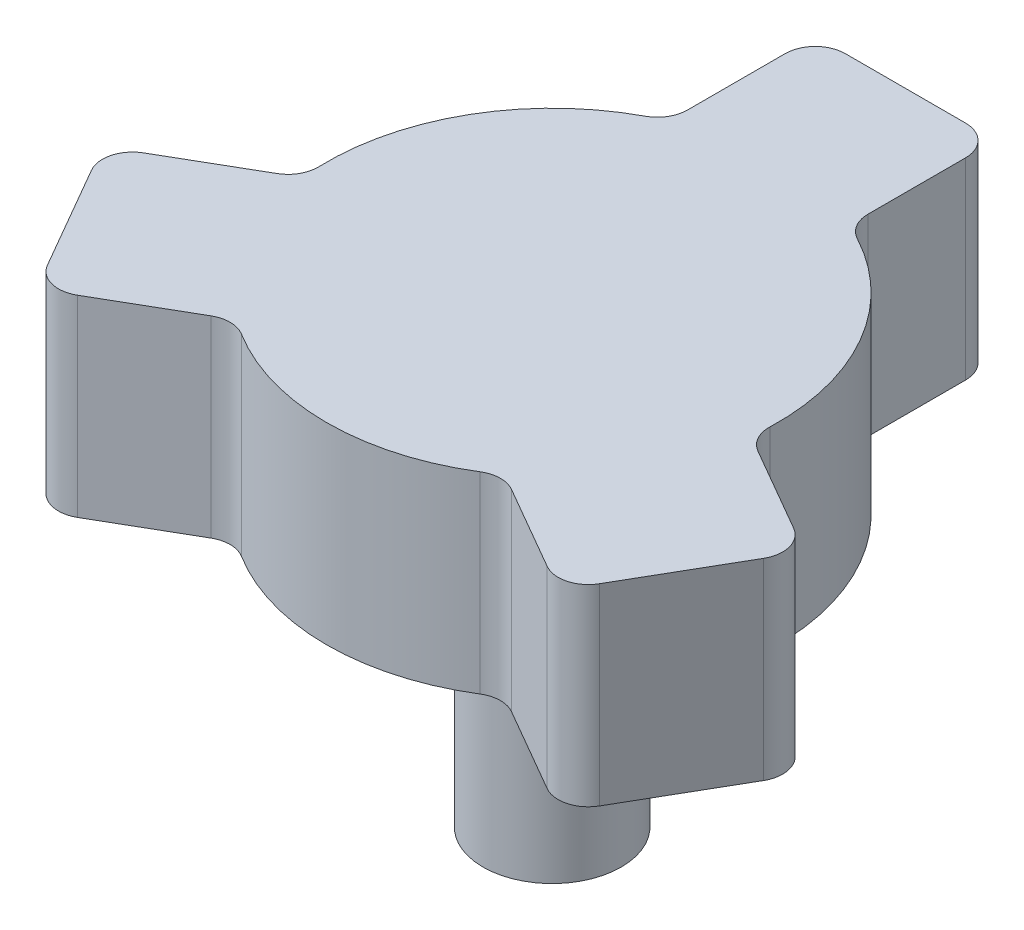
SolidWorks part; units mm, degrees
ref_plane "Front Plane" through (0, 0, 0) normal (0, 0, 1) x (1, 0, 0)
ref_plane "Top Plane" through (0, 0, 0) normal (0, 1, 0) x (1, 0, 0)
ref_plane "Right Plane" through (0, 0, 0) normal (1, 0, 0) x (0, 0, -1)
ref_axis "Axis1" through (0, 0, 0) along (0, 1, 0)
sketch "Sketch1" plane through (0, 0, 0) normal (0, 1, 0) x (1, 0, 0)
  circle A0 centre (0, 0) radius 9.525
  dimension "D1" = 19.05
extrude "Boss-Extrude1" add sketch "Sketch1" along normal blind 8.128
sketch "Sketch2" plane through (0, 8.128, 0) normal (0, 1, 0) x (1, 0, 0)
  line L1 (-3.81, 14.9208) -> (3.81, 14.9208)
  line L2 (-3.81, 14.9208) -> (-3.81, 0.3158)
  line L3 (-3.81, 0.3158) -> (3.81, 0.3158)
  line L4 (3.81, 14.9208) -> (3.81, 0.3158)
  line L5 (-3.81, 14.9208) -> (3.81, 0.3158) construction
  line L6 (-3.81, 0.3158) -> (3.81, 14.9208) construction
  point P0 (0, 7.6183)
  dimension "D1" = 7.62
  dimension "D2" = 14.605
extrude "Boss-Extrude2" add sketch "Sketch2" against normal through all
fillet "Fillet1" radius 1.27 4 edges at (3.81, 4.064, -8.7298) (3.81, 4.064, -14.9208) (-3.81, 4.064, -8.7298) (-3.81, 4.064, -14.9208)
pattern_circular "CirPattern1" count 3 over 360 about axis through (0, 0, 0) along (0, 1, 0) of "Boss-Extrude2", "Fillet1"
sketch "Sketch3" plane through (0, 0, 0) normal (0, -1, 0) x (1, 0, 0)
  circle A0 centre (0, 0) radius 2.921
  dimension "D1" = 5.842
extrude "Boss-Extrude3" add sketch "Sketch3" along normal blind 11.43
